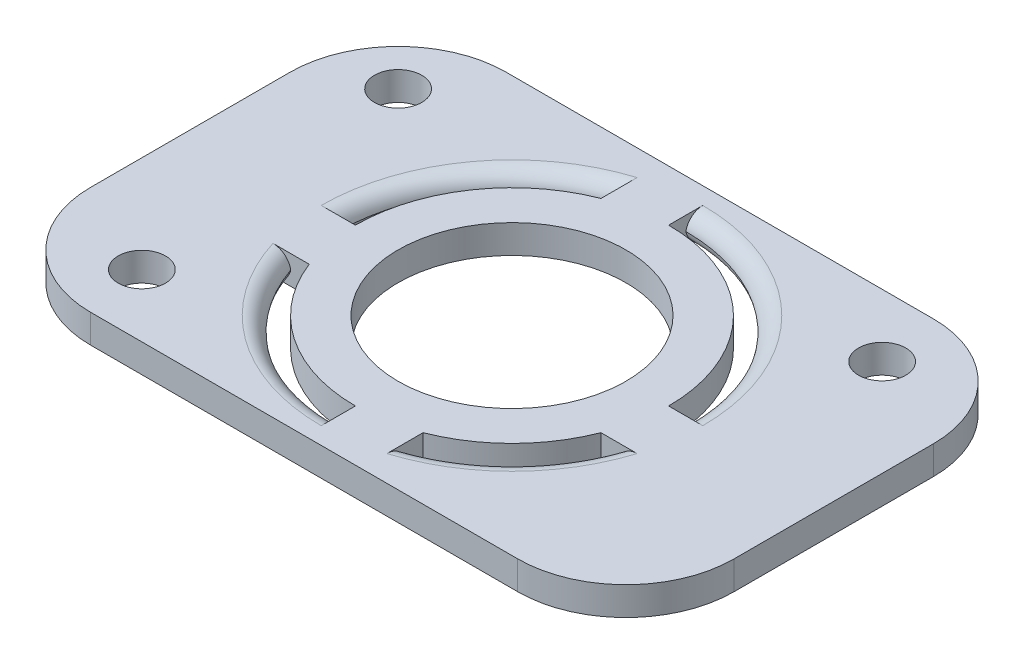
SolidWorks part; units mm, degrees
ref_plane "Alzado" through (0, 0, 0) normal (0, 0, 1) x (1, 0, 0)
ref_plane "Planta" through (0, 0, 0) normal (0, 1, 0) x (1, 0, 0)
ref_plane "Vista lateral" through (0, 0, 0) normal (1, 0, 0) x (0, 0, -1)
sketch "Sketch1" plane through (0, 0, 0) normal (0, 1, 0) x (1, 0, 0)
  line L1 (-57.5, 37.5) -> (57.5, 37.5)
  line L2 (-57.5, 37.5) -> (-57.5, -37.5)
  line L3 (-57.5, -37.5) -> (57.5, -37.5)
  line L4 (57.5, 37.5) -> (57.5, -37.5)
  circle A0 centre (-44.48, 24.48) radius 4.15
  point P0 (0, 0)
  dimension "D10" = 8.3
  dimension "D1" = 75
  dimension "D2" = 115
  dimension "D3" = 37.5
  dimension "D4" = 57.5
  dimension "D5" = 13.02
  dimension "D9" = 13.02
extrude "Boss-Extrude1" add sketch "Sketch1" along normal blind 5
fillet "Fillet1" radius 20 4 edges at (-57.5, 2.5, 37.5) (-57.5, 2.5, -37.5) (57.5, 2.5, -37.5) (57.5, 2.5, 37.5)
sketch "Sketch5" plane through (0, 0, 0) normal (0, -1, 0) x (1, 0, 0)
  line L0 (-37.5, 37.5) -> (37.5, 37.5) construction
  line L1 (-57.5, -17.5) -> (-57.5, 17.5) construction
  line L2 (37.5, -37.5) -> (-37.5, -37.5) construction
  line L3 (57.5, 17.5) -> (57.5, -17.5) construction
  circle A0 centre (-39.5, 25.5) radius 4.15
  circle A1 centre (39.5, -25.5) radius 4.15
  dimension "D5" = 8.3
  dimension "D6" = 8.3
  dimension "D1" = 12
  dimension "D2" = 18
  dimension "D3" = 12
  dimension "D4" = 18
extrude "Cut-Extrude4" cut sketch "Sketch5" against normal blind 10
sketch "Sketch8" plane through (0, 0, 0) normal (0, -1, 0) x (1, 0, 0)
sketch "Sketch11" plane through (0, 5, 0) normal (0, 1, 0) x (1, 0, 0)
  line L0 (57.5, -17.5) -> (57.5, 17.5) construction
  line L1 (-37.5, -37.5) -> (37.5, -37.5) construction
  line L2 (-57.5, 17.5) -> (-57.5, -17.5) construction
  line L3 (37.5, 37.5) -> (-37.5, 37.5) construction
  line L4 (57.5, -17.5) -> (57.5, 17.5)
  line L5 (-37.5, -37.5) -> (37.5, -37.5)
  line L6 (-57.5, 17.5) -> (-57.5, -17.5)
  line L7 (37.5, 37.5) -> (-37.5, 37.5)
  line L8 (37.5, 36.5) -> (-37.5, 36.5)
  line L9 (-56.5, 17.5) -> (-56.5, -17.5)
  line L10 (-37.5, -36.5) -> (37.5, -36.5)
  line L11 (56.5, -17.5) -> (56.5, 17.5)
  arc A0 (57.5, 17.5) -> (37.5, 37.5) centre (37.5, 17.5) ccw construction
  arc A1 (37.5, -37.5) -> (57.5, -17.5) centre (37.5, -17.5) ccw construction
  arc A2 (-57.5, -17.5) -> (-37.5, -37.5) centre (-37.5, -17.5) ccw construction
  arc A3 (-37.5, 37.5) -> (-57.5, 17.5) centre (-37.5, 17.5) ccw construction
  arc A4 (57.5, 17.5) -> (37.5, 37.5) centre (37.5, 17.5) ccw
  arc A5 (37.5, -37.5) -> (57.5, -17.5) centre (37.5, -17.5) ccw
  arc A6 (-57.5, -17.5) -> (-37.5, -37.5) centre (-37.5, -17.5) ccw
  arc A7 (-37.5, 37.5) -> (-57.5, 17.5) centre (-37.5, 17.5) ccw
  arc A8 (-37.5, 36.5) -> (-56.5, 17.5) centre (-37.5, 17.5) ccw
  arc A9 (-56.5, -17.5) -> (-37.5, -36.5) centre (-37.5, -17.5) ccw
  arc A10 (37.5, -36.5) -> (56.5, -17.5) centre (37.5, -17.5) ccw
  arc A11 (56.5, 17.5) -> (37.5, 36.5) centre (37.5, 17.5) ccw
  dimension "D1" = 1
extrude "Cut-Extrude7" cut sketch "Sketch11" against normal blind 16 contours A4 L7 A7 L6 A6 L5 A5 L4 | L8 A8 L9 A9 L10 A10 L11 A11
sketch "Sketch12" plane through (0, 5, 0) normal (0, 1, 0) x (1, 0, 0)
  line L0 (0, 30.5) -> (0, 27.5)
  line L1 (-30.5, 0) -> (-27.5, 0)
  line L2 (27.5, 0) -> (30.5, 0)
  line L3 (0, -30.5) -> (0, -27.5)
  line L4 (-28.8141, -10) -> (-25.6174, -10)
  line L5 (-10, 28.8141) -> (-10, 25.6174)
  line L6 (25.6174, -10) -> (28.8141, -10)
  line L7 (10, -28.8141) -> (10, -25.6174)
  line L8 (-10, 30.5) -> (-10, 27.5) construction
  line L9 (27.5, -10) -> (30.5, -10) construction
  line L10 (10, -30.5) -> (10, -27.5) construction
  line L11 (-30.5, -10) -> (-27.5, -10) construction
  arc A0 (-10, 28.8141) -> (-30.5, 0) centre (0, 0) ccw
  arc A1 (-10, 25.6174) -> (-27.5, 0) centre (0, 0) ccw
  circle A3 centre (0, 0) radius 20
  arc A4 (30.5, 0) -> (0, 30.5) centre (0, 0) ccw
  arc A5 (27.5, 0) -> (0, 27.5) centre (0, 0) ccw
  arc A6 (10, -28.8141) -> (28.8141, -10) centre (0, 0) ccw
  arc A7 (10, -25.6174) -> (25.6174, -10) centre (0, 0) ccw
  arc A8 (-28.8141, -10) -> (0, -30.5) centre (0, 0) ccw
  arc A9 (-25.6174, -10) -> (0, -27.5) centre (0, 0) ccw
  dimension "D2" = 40
  dimension "D3" = 55
  dimension "D4" = 3
  dimension "D5" = 10
extrude "Cut-Extrude8" cut sketch "Sketch12" against normal blind 10
fillet "Fillet2" radius 3 8 edges at (-17.6812, 0, 24.8521) (-24.8521, 0, -17.6812) (21.5668, 0, -21.5668) (21.5668, 0, 21.5668) (-17.6812, 5, 24.8521) (-24.8521, 5, -17.6812) (21.5668, 5, 21.5668) (21.5668, 5, -21.5668)
